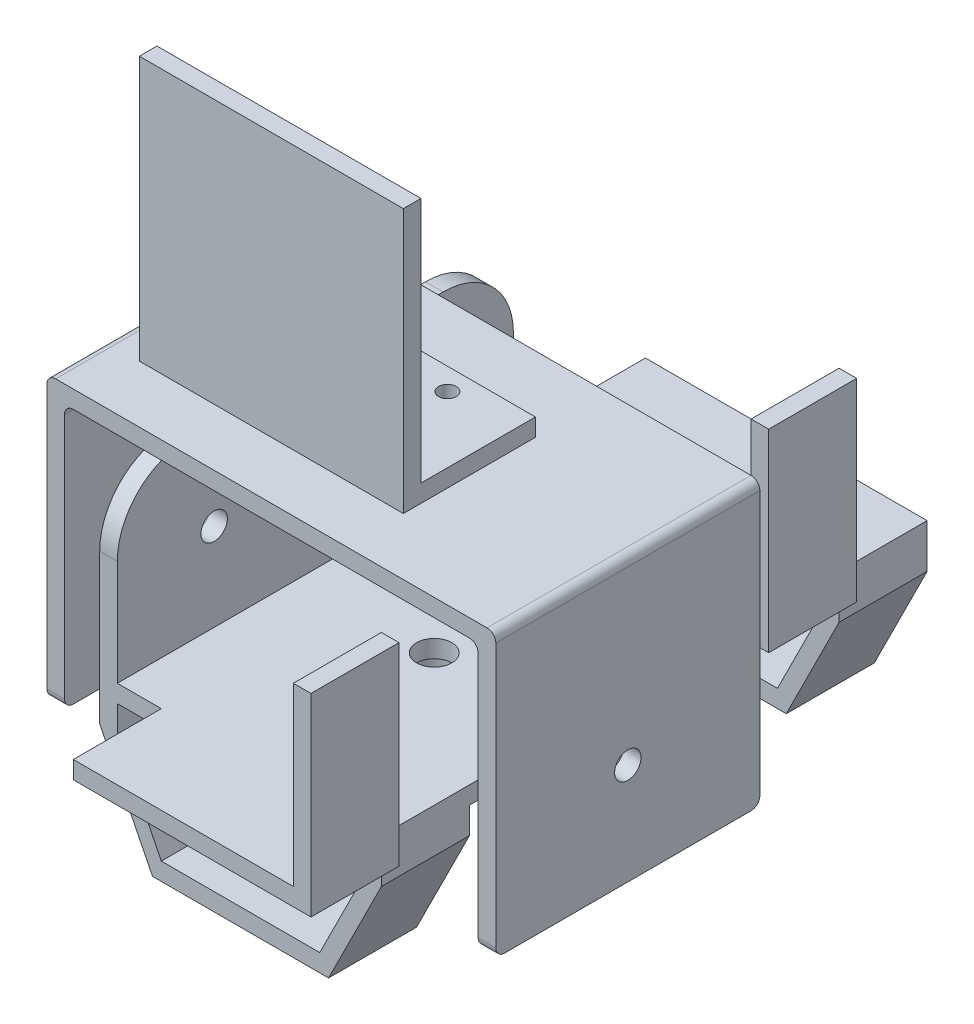
SolidWorks part; units mm, degrees
note: The reader was unsure of these and kept them because the rebuilt part matched: shared geometry of "Sketch4<2>", "Sketch21<3>".
other "MotorHub(bottom)"
other "Bracket(top)"
other "Bracket(bottom)"
other "MotorHub(top)" parameters "D1"=18.7171, "D2"=8.591, "D3"=33.3412, "D4"=5.2478, "D5"=40, "D6"=23.3238, "D7"=12, "D8"=12
ref_plane "Front Plane" through (0, 0, 0) normal (0, 0, 1) x (1, 0, 0)
ref_plane "Top Plane" through (0, 0, 0) normal (0, 1, 0) x (1, 0, 0)
ref_plane "Right Plane" through (0, 0, 0) normal (1, 0, 0) x (0, 0, -1)
sketch "Sketch4" plane through (0, 0, 0) normal (0, 0, 1) x (1, 0, 0)
  line L0 (-17, 20) -> (-17, -2)
  line L1 (-17, -2) -> (15, -2)
  line L5 (15, 0) -> (-15, 0)
  line L6 (-15, 0) -> (-15, 20)
  line L7 (-15, 20) -> (-17, 20)
  line L8 (15, 0) -> (15, -2)
  dimension "D2" = 2
  dimension "D3" = 30
  dimension "D4" = 20
  dimension "D1" = 2
extrude "Boss-Extrude1" add sketch "Sketch4" along normal mid plane 42
extrude "Boss-Extrude16" add sketch "Sketch4<2>" against normal blind 20 from surface at -21 starting at face at (-5.6667, 6, -21)
sketch "Sketch4<2>" plane through (0, 0, 0) normal (0, 0, 1) x (1, 0, 0) same geometry as "Sketch4"
sketch "Sketch23" plane through (-15, 0, 0) normal (1, 0, 0) x (0, 0, -1)
  line L0 (24, 20) -> (24, 0)
  line L1 (-21, 20) -> (41, 20) construction
  line L2 (-21, 0) -> (41, 0) construction
  line L3 (24, 0) -> (41, 0)
  line L4 (41, 0) -> (41, 20)
  line L5 (41, 20) -> (24, 20)
  dimension "D1" = 17
extrude "Cut-Extrude4" cut sketch "Sketch23" against normal up to next
fillet "Fillet1" radius 8 2 edges at (-16, 20, 21) (-16, 20, -24)
sketch "Sketch11" plane through (0, 0, 21) normal (0, 0, 1) x (1, 0, 0)
  line L0 (-10, 0) -> (-10, -2)
  line L1 (15, 0) -> (-15, 0) construction
  line L2 (-17, -2) -> (15, -2) construction
  line L3 (-10, -2) -> (17, -2)
  line L4 (17, -2) -> (17, 20)
  line L5 (17, 20) -> (15, 20)
  line L6 (15, 20) -> (15, 0)
  line L7 (15, 0) -> (-10, 0)
  line L8 (-15, 0) -> (-15, 12) construction
  line L9 (-15, 20) -> (-17, 20) construction
  dimension "D1" = 5
  dimension "D2" = 30
extrude "Boss-Extrude5" add sketch "Sketch11" along normal blind 10
mirror "Mirror1" about plane through (0, 0, 0) normal (0, 0, 1) of "Boss-Extrude5"
sketch "Sketch21" plane through (0, 0, 31) normal (0, 0, 1) x (1, 0, 0)
  line L0 (15, -2) -> (15, -5)
  line L1 (9, -17) -> (-11, -17)
  line L2 (-17, -5) -> (-17, -2)
  line L3 (-17, -2) -> (-15, -2)
  line L4 (-17, -2) -> (-10, -2) construction
  line L5 (-15, -2) -> (-15, -5)
  line L6 (-10, -15) -> (8, -15)
  line L7 (13, -5) -> (13, -2)
  line L9 (13, -2) -> (15, -2)
  line L11 (-10, -2) -> (17, -2) construction
  line L12 (-15, -5) -> (-10, -15)
  line L13 (8, -15) -> (13, -5)
  line L14 (-17, -5) -> (-11, -17)
  line L15 (9, -17) -> (15, -5)
  dimension "D1" = 2
  dimension "D2" = 2
  dimension "D3" = 15
  dimension "D4" = 10
  dimension "D5" = 5
  dimension "D6" = 5
extrude "Boss-Extrude14" add sketch "Sketch21" against normal blind 10 from offset 10 contours L1 L14 L2 L3 L5 L12 L6 L13 L7 L9 L0 L15 offset against normal yes
extrude "Boss-Extrude15" add sketch "Sketch21<3>" against normal blind 10 from offset 62 offset against normal yes
sketch "Sketch21<3>" plane through (0, 0, 31) normal (0, 0, 1) x (1, 0, 0) same geometry as "Sketch21"
sketch "Sketch5" plane through (0, 0, 0) normal (0, 1, 0) x (1, 0, 0)
  circle A0 centre (0, 0) radius 2
  dimension "D1" = 4
extrude "Cut-Extrude1" cut sketch "Sketch5" against normal up to next
sketch "Sketch6" plane through (0, 0, 0) normal (0, 0, 1) x (1, 0, 0)
  line L0 (-17, -1.55) -> (-17, 28.45)
  line L1 (-17, 12) -> (-17, -5) construction
  line L2 (-17, 28.45) -> (30, 28.45)
  line L3 (30, 28.45) -> (30, -1.55)
  line L4 (15, 20) -> (15, 0) construction
  line L5 (30, -1.55) -> (32, -1.55)
  line L6 (32, -1.55) -> (32, 30.45)
  line L7 (32, 30.45) -> (-19, 30.45)
  line L8 (-19, 30.45) -> (-19, -1.55)
  line L9 (-19, -1.55) -> (-17, -1.55)
  line L11 (32, 9.95) -> (4.3333, 9.95) construction
  line L13 (15, 0) -> (-10, 0) construction
  dimension "D2" = 2
  dimension "D1" = 30
  dimension "D3" = 2
  dimension "D5" = 15
  dimension "D4" = 9.95
  dimension "D6" = 11.5
extrude "Boss-Extrude2" add sketch "Sketch6" along normal mid plane 30 from offset 10 separate body
ref_plane "Plane1" through (0, 0, 10) normal (0, 0, -1) x (-1, 0, 0)
sketch "Sketch24" plane through (0, 0, 10) normal (0, 0, -1) x (-1, 0, 0)
  line L0 (-20, 28.45) -> (-30, 22.45)
  line L1 (17, 28.45) -> (-30, 28.45) construction
  line L2 (-30, 28.45) -> (-30, -1.55) construction
  line L3 (-30, 22.45) -> (-30, 28.45)
  line L4 (-30, 28.45) -> (-20, 28.45)
  line L5 (12, 28.45) -> (17, 23.45)
  line L6 (17, -1.55) -> (17, 28.45) construction
  line L7 (17, 23.45) -> (17, 28.45)
  line L8 (17, 28.45) -> (12, 28.45)
  dimension "D1" = 5
  dimension "D2" = 5
  dimension "D3" = 6
  dimension "D4" = 10
extrude "Boss-Extrude17" add sketch "Sketch24" along normal mid plane 10
sketch "Sketch7" plane through (32, 0, 0) normal (1, 0, 0) x (0, 0, -1)
  line L0 (-10, 9.95) -> (-10, -1.55) construction
  line L1 (-25, -1.55) -> (5, -1.55) construction
  circle A0 centre (-10, 9.95) radius 1.5
  dimension "D1" = 3
extrude "Cut-Extrude2" cut sketch "Sketch7" against normal through all
sketch "Sketch8" plane through (0, -2, 0) normal (0, -1, 0) x (1, 0, 0)
  circle A0 centre (0, 0) radius 2.5
  circle A1 centre (0, 0) radius 7.5
  circle A2 centre (0, 0) radius 5 construction
  dimension "D1" = 5
  dimension "D2" = 15
  dimension "D3" = 10
extrude "Boss-Extrude3" add sketch "Sketch8" along normal blind 2 separate body contours A1 A2 | A2 A0
sketch "Sketch16" plane through (0, -4, 0) normal (0, -1, 0) x (1, 0, 0)
  circle A0 centre (0, 0) radius 5 construction
  circle A1 centre (0, 0) radius 5
  circle A2 centre (0, 0) radius 2.5 construction
  circle A3 centre (0, 0) radius 2.5
extrude "Boss-Extrude7" add sketch "Sketch16" along normal blind 7
sketch "Sketch17" plane through (30, 0, 0) normal (-1, 0, 0) x (0, 0, -1)
  circle A0 centre (-10, -9.95) radius 2.5
  circle A1 centre (-10, -9.95) radius 10.5
  circle A2 centre (-10, -9.95) radius 5 construction
  dimension "D1" = 5
  dimension "D2" = 21
  dimension "D3" = 10
extrude "Boss-Extrude8" add sketch "Sketch17" along normal blind 2 separate body contours A0 | A1
sketch "Sketch18" plane through (28, 0, 0) normal (-1, 0, 0) x (0, 0, 1)
  circle A0 centre (10, 9.95) radius 5 construction
  circle A1 centre (10, 9.95) radius 2.5 construction
  circle A2 centre (10, 9.95) radius 5
  circle A3 centre (10, 9.95) radius 2.5
extrude "Boss-Extrude9" add sketch "Sketch18" along normal blind 7
sketch "Sketch14" plane through (0, 0, 0) normal (1, 0, 0) x (0, 0, -1)
  line L0 (-3.5, 30.45) -> (-18.5, 30.45)
  line L1 (-25, 30.45) -> (5, 30.45) construction
  line L2 (-18.5, 30.45) -> (-18.5, 60.45)
  line L3 (-18.5, 60.45) -> (-16.5, 60.45)
  line L4 (-16.5, 60.45) -> (-16.5, 32.45)
  line L5 (-16.5, 32.45) -> (-3.5, 32.45)
  line L6 (-3.5, 32.45) -> (-3.5, 30.45)
  line L7 (-10, 32.45) -> (-10, -1.55) construction
  line L8 (-25, -1.55) -> (5, -1.55) construction
  dimension "D1" = 2
  dimension "D2" = 2
  dimension "D3" = 30
  dimension "D4" = 15
extrude "Boss-Extrude6" add sketch "Sketch14" along normal mid plane 30 separate body
sketch "Sketch19" plane through (0, 32.45, 0) normal (0, 1, 0) x (1, 0, 0)
  line L0 (0, -16.5) -> (0, -10) construction
  line L1 (-7.5, -6) -> (7.5, -6) construction
  line L2 (-7.5, -6) -> (-7.5, -14) construction
  line L3 (-7.5, -14) -> (7.5, -14) construction
  line L4 (7.5, -6) -> (7.5, -14) construction
  line L5 (-7.5, -6) -> (7.5, -14) construction
  line L6 (-7.5, -14) -> (7.5, -6) construction
  line L7 (15, -16.5) -> (-15, -16.5) construction
  line L8 (0, -10) -> (15, -10) construction
  line L9 (15, -3.5) -> (15, -16.5) construction
  circle A0 centre (-7.5, -6) radius 1
  circle A1 centre (7.5, -6) radius 1
  circle A2 centre (7.5, -14) radius 1
  circle A3 centre (-7.5, -14) radius 1
  dimension "D3" = 2
  dimension "D1" = 15
  dimension "D2" = 8
extrude "Cut-Extrude3" cut sketch "Sketch19" against normal up to surface (4 mm away)
fillet "Fillet2" radius 1 8 edges at (-18, -1.55, 25) (-18, -1.55, -5) (31, -1.55, -5) (31, -1.55, 25) (30, 28.45, 20) (-17, 28.45, 20) (-19, 30.45, 10) (32, 30.45, 10)
other "Save Bodies1"
equation "\"Thick\"=2"
equation "\"D2@Sketch4\"=\"Thick\""
equation "\"D2@Sketch6\"=\"Thick\""
equation "\"D3@Sketch6\"=\"Thick\""
equation "\"D1@Sketch4\"=\"Thick\""
